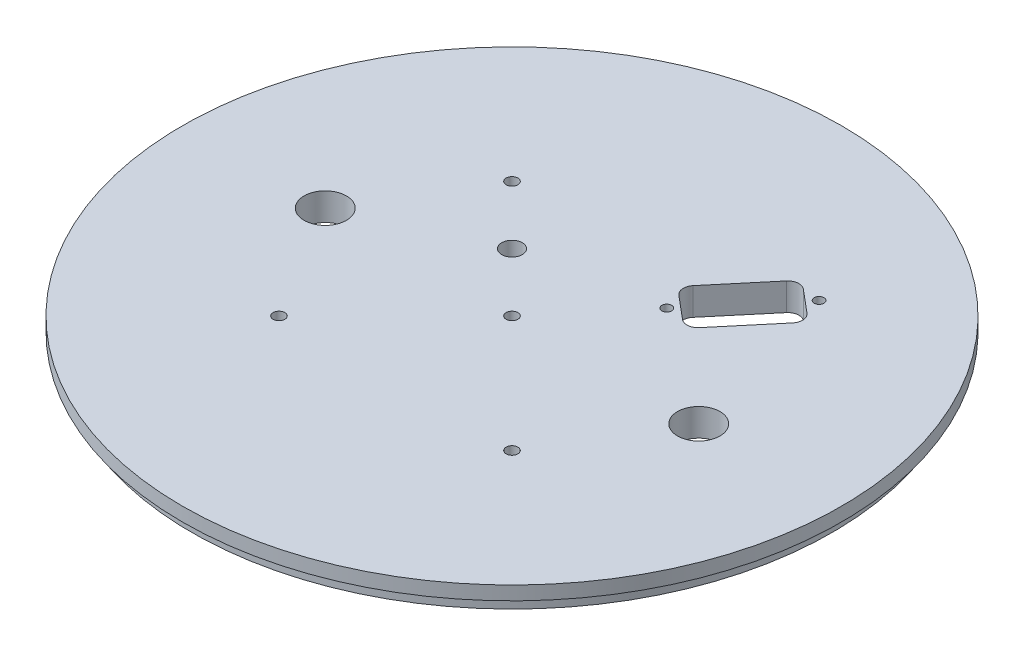
SolidWorks part; units mm, degrees
material "6061-T6 (SS)"
ref_plane "Front Plane" through (0, 0, 0) normal (0, 0, 1) x (1, 0, 0)
ref_plane "Top Plane" through (0, 0, 0) normal (0, 1, 0) x (1, 0, 0)
ref_plane "Right Plane" through (0, 0, 0) normal (1, 0, 0) x (0, 0, -1)
sketch "Sketch1" plane through (0, 0, 0) normal (0, 1, 0) x (1, 0, 0)
  line L0 (0, -76.2) -> (0, 76.2) construction
  line L1 (-76.2, 0) -> (76.2, 0) construction
  line L2 (-26.9408, 26.9408) -> (0, 0) construction
  line L3 (0, 56.7387) -> (0, 29.6936) construction
  line L4 (3.6407, 56.7387) -> (3.6407, 29.6936) construction
  line L5 (-3.6407, 56.7387) -> (-3.6407, 29.6936) construction
  line L6 (0, -56.7387) -> (0, -29.6936) construction
  line L7 (3.6407, -56.7387) -> (3.6407, -29.6936) construction
  line L8 (-3.6407, -56.7387) -> (-3.6407, -29.6936) construction
  line L9 (-53.8815, -53.8815) -> (54.3236, 54.3236) construction
  line L10 (-26.9408, -26.9408) -> (0, 0) construction
  circle A0 centre (0, 0) radius 76.2
  circle A1 centre (0, 0) radius 3.175 construction
  circle A2 centre (43.18, 0) radius 4.9022
  circle A3 centre (-43.18, 0) radius 4.9022
  circle A4 centre (-26.9408, 26.9408) radius 1.3589
  arc A6 (3.6407, 56.7387) -> (-3.6407, 56.7387) centre (0, 56.7387) ccw construction
  arc A7 (-3.6407, 29.6936) -> (3.6407, 29.6936) centre (0, 29.6936) ccw construction
  arc A8 (3.6407, -56.7387) -> (-3.6407, -56.7387) centre (0, -56.7387) cw construction
  arc A9 (-3.6407, -29.6936) -> (3.6407, -29.6936) centre (0, -29.6936) cw construction
  circle A10 centre (26.9408, -26.9408) radius 1.3589
  circle A11 centre (-13.4704, 13.4704) radius 2.3813
  circle A13 centre (-26.9408, -26.9408) radius 1.3589
  circle A14 centre (0, 0) radius 38.1 construction
  circle A15 centre (0, 0) radius 1.3589
  point P16 (0, 43.2162)
  point P19 (0, 0)
  point P26 (0, -43.2162)
  dimension "D1" = 152.4
  dimension "D2" = 6.35
  dimension "D3" = 9.8044
  dimension "D5" = 2.7178
  dimension "D8" = 4.7625
  dimension "D10" = 2.7178
  dimension "D12" = 2.7178
  dimension "D6" = 38.1
  dimension "D7" = 45
  dimension "D4" = 45
  dimension "D9" = 43.18
  dimension "D11" = 38.1
extrude "Boss-Extrude1" add sketch "Sketch1" along normal blind 6.35
sketch "Sketch2" plane through (0, 0, 0) normal (0, -1, 0) x (1, 0, 0)
  circle A0 centre (0, 0) radius 76.2
  circle A1 centre (0, 0) radius 74.041
  dimension "D1" = 152.4
  dimension "D2" = 148.082
extrude "Cut-Extrude1" cut sketch "Sketch2" against normal blind 3.175
sketch "Sketch3" plane through (0, 6.35, 0) normal (0, 1, 0) x (1, 0, 0)
  line L0 (0, 76.2) -> (0, -76.2) construction
  line L1 (-76.2, 0) -> (76.2, 0) construction
  line L2 (0, 34.798) -> (0, 13.97) construction
  line L3 (3.2385, 34.798) -> (3.2385, 13.97)
  line L4 (-3.2385, 34.798) -> (-3.2385, 13.97)
  line L5 (0, -34.798) -> (0, -13.97) construction
  line L6 (3.2385, -34.798) -> (3.2385, -13.97)
  line L7 (-3.2385, -34.798) -> (-3.2385, -13.97)
  circle A0 centre (0, 0) radius 76.2 construction
  arc A1 (3.2385, 34.798) -> (-3.2385, 34.798) centre (0, 34.798) ccw
  arc A2 (-3.2385, 13.97) -> (3.2385, 13.97) centre (0, 13.97) ccw
  arc A3 (3.2385, -34.798) -> (-3.2385, -34.798) centre (0, -34.798) cw
  arc A4 (-3.2385, -13.97) -> (3.2385, -13.97) centre (0, -13.97) cw
  point P7 (0, 13.97)
  point P8 (0, 34.798)
  point P12 (0, 24.384)
  point P20 (0, -24.384)
  point P25 (0, -34.798)
  point P26 (0, -13.97)
  dimension "D1" = 13.97
  dimension "D2" = 20.828
  dimension "D3" = 6.477
extrude "Cut-Extrude2" cut sketch "Sketch3" against normal blind 3.556 from offset 3.175 offset against normal yes
hole_wizard "Tap Drill for #4-40 Tap1" positions "Sketch5" profile "Sketch6" hole size "#4-40" standard "ANSI Inch" end condition through all
sketch "Sketch5" plane through (0, 6.35, 0) normal (0, 1, 0) x (1, 0, 0)
  line L0 (0, 0) -> (53.6567, 63.9455) construction
  line L2 (0, 0) -> (43.18, 0) construction
  point P0 (16.3268, 19.4575)
  point P2 (32.3965, 38.6086)
  dimension "D1" = 50
  dimension "D2" = 25
  dimension "D3" = 25.4
sketch "Sketch6" plane through (16.3268, 6.35, -19.4575) normal (1, 0, 0) x (0, 0, 1)
  line L0 (0, 0) -> (0, 6.35)
  line L1 (0, 6.35) -> (1.1303, 6.35)
  line L2 (1.1303, 6.35) -> (1.1303, 0)
  line L5 (1.1303, 0) -> (0, 0)
  line L11 (0, -6.35) -> (0, 107.95) construction
  dimension "Thru Hole Dia." = 2.2606
  dimension "Thru Hole Depth" = 6.35
sketch "Sketch4" plane through (0, 6.35, 0) normal (0, 1, 0) x (1, 0, 0)
  line L0 (15.1695, 23.4128) -> (20.423, 19.0046)
  line L1 (14.8564, 26.9913) -> (24.7219, 38.7485)
  line L2 (24.0014, 19.3177) -> (33.8669, 31.0749)
  line L3 (28.3003, 39.0616) -> (33.5538, 34.6533)
  line L4 (0, 0) -> (32.3965, 38.6086) construction
  circle A1 centre (16.3268, 19.4575) radius 1.1303 construction
  arc A2 (24.7219, 38.7485) -> (28.3003, 39.0616) centre (26.6676, 37.1158) cw
  arc A3 (33.8669, 31.0749) -> (33.5538, 34.6533) centre (31.9212, 32.7076) ccw
  arc A4 (20.423, 19.0046) -> (24.0014, 19.3177) centre (22.0557, 20.9503) ccw
  arc A5 (14.8564, 26.9913) -> (15.1695, 23.4128) centre (16.8021, 25.3586) ccw
  point P11 (17.7962, 21.2087)
  dimension "D4" = 2.54
  dimension "D1" = 2.286
  dimension "D2" = 2.286
  dimension "D3" = 11.938
extrude "Cut-Extrude3" cut sketch "Sketch4" against normal through all
equation "\"leadDist\"=1.5"
equation "\"Lead_Screw_Dist\"= 3.4in"
equation "\"D9@Sketch1\"=\"Lead_Screw_Dist\"/2"
equation "\"Lead_Screw_Diam\"= 0.386in"
equation "\"D3@Sketch1\"=\"Lead_Screw_Diam\""
equation "\"Bodytube_OD\"= 6.17in"
equation "\"Bodytube_ID\"= 5.998in"
equation "\"Motor_OD\"= 4in"
equation "\"Fwd_Tube_Length\"= 40in"
equation "\"Mid_Tube_Length\"= 1in"
equation "\"Aft_Section_Length\"= 39in"
equation "\"AB_Coupler_OD_Length\"= 1in"
equation "\"AB_Coupling_Section_Length\"= 0.375in"
equation "\"AB_Coupler_Length\"= \"AB_Coupler_OD_Length\" + \"AB_Coupling_Section_Length\" * 2"
equation "\"Cutout_Angle\"= 80"
equation "\"AB_Paddle_Height\"= 0.375in"
equation "\"AB_Coupler_Num_Screws\"= 4"
equation "\"Num_Cutouts\"= 3"
equation "\"AB_Coupler_OD\"= 6.17in"
equation "\"AB_Coupler_ID\"= 5.75in"
equation "\"AB_Coupler_Surface_Diameter\"= 5.998in"
equation "\"AB_Coupling_Screw_Diameter\"= 0.15748in"
equation "\"AB_Central_Bushing_Length\"= .4724in"
equation "\"Lead_Screw_Length\"= (\"Mid_Coupler_Length\" + 2*0.375in + 2*0.5in)"
equation "\"Paddle_Pin_Offset\"= .25in"
equation "\"Paddle_Pin_Radius\"= 2.25in"
equation "\"SS_Paddle_Pin_Radius\"= 2.25*0.66in"
equation "\"Paddle_Gear_OD\"= 3.2in"
equation "\"Drive_Gear_OD\"= 1.7in"
equation "\"Fwd_BKHD_From_Top\"= 18in"
equation "\"Fin_Thickness\"= .118in"
equation "\"Guiderail_Cutout_Diameter\"= 1.5in"
equation "\"DB9_Hole_Dist\"= 25mm"
equation "\"Airbrakes_Wire_Hole_Dia\"= .25in"
equation "\"Airbrakes_Wire_Hole_Dist\"= 1.1in"
equation "\"Servo_Gear_Offset\"= 0.5in"
equation "\"Mid_Coupler_Length\"= 13in"
equation "\"D2@Sketch5\"=\"DB9_Hole_Dist\""
equation "\"DB9_Relief_Width\"= 0.47in"
equation "\"DB9_Relief_Hole_Offset\"= 0.09in"
equation "\"D1@Sketch4\"=\"DB9_Relief_Hole_Offset\""
equation "\"D2@Sketch4\"=\"DB9_Relief_Hole_Offset\""
equation "\"D3@Sketch4\"=\"DB9_Relief_Width\""
